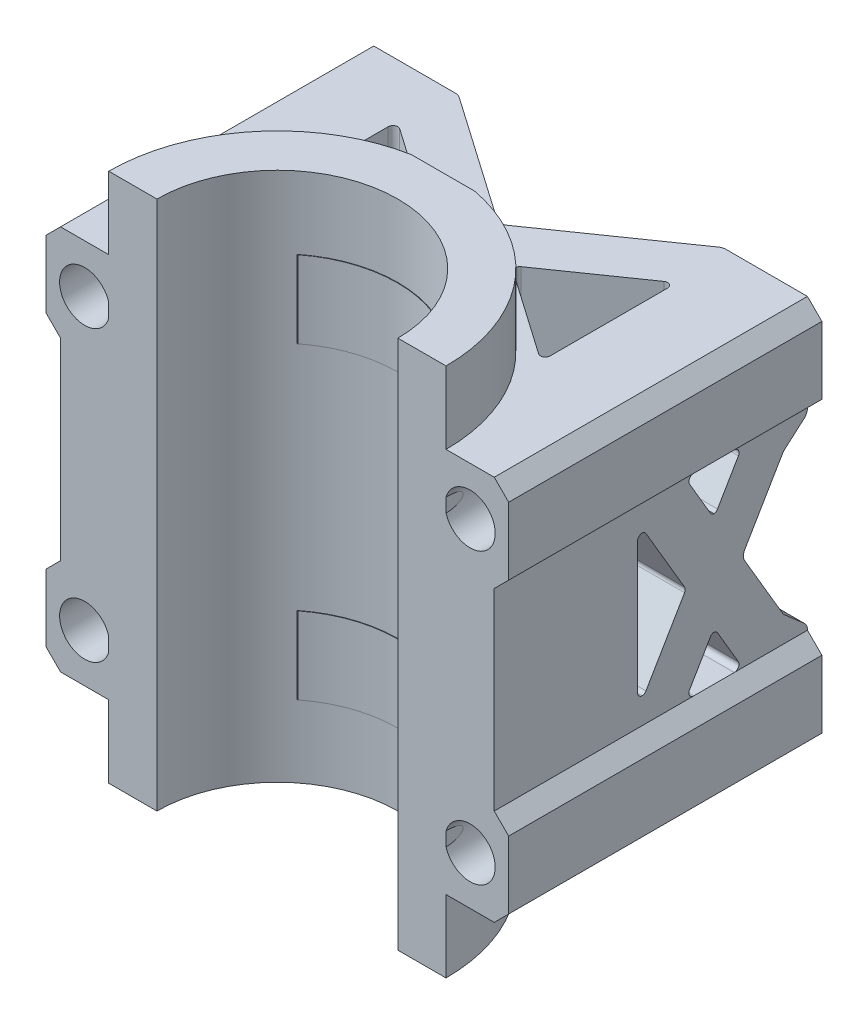
SolidWorks part; units mm, degrees
ref_plane "Front Plane" through (0, 0, 0) normal (0, 0, 1) x (1, 0, 0)
ref_plane "Top Plane" through (0, 0, 0) normal (0, 1, 0) x (1, 0, 0)
ref_plane "Right Plane" through (0, 0, 0) normal (1, 0, 0) x (0, 0, -1)
sketch "Sketch1" plane through (0, 0, 0) normal (0, 1, 0) x (1, 0, 0)
  line L0 (-12.5, 0) -> (-17.5, 0)
  line L1 (12.5, 0) -> (17.5, 0)
  line L2 (0, 0) -> (0, 12.5)
  line L4 (-0.3449, 17.192) -> (3.2687, 17.192)
  line L5 (3.2687, 17.192) -> (-3.2687, 17.192)
  arc A0 (12.5, 0) -> (-12.5, 0) centre (0, 0) ccw
  arc A1 (17.5, 0) -> (3.2687, 17.192) centre (0, 0) ccw
  arc A2 (-3.2687, 17.192) -> (-17.5, 0) centre (0, 0) ccw
  dimension "D1" = 25
  dimension "D2" = 35
extrude "Boss-Extrude1" add sketch "Sketch1" along normal blind 55 contours L5 A2 L0 A0 L1 A1 L4
sketch "Sketch4" plane through (0, 0, 0) normal (0, 0, 1) x (1, 0, 0)
  line L0 (0, -9.4556) -> (0, 9.4556) construction
  line L1 (-23.9986, 16.0014) -> (-22.5, 17.5)
  line L9 (-14.5, 27.5) -> (-19.9986, 27.5) construction
  line L24 (-23.9986, 8.9986) -> (-23.9986, 16.0014)
  line L27 (14.5, 7.5) -> (14.5, 12.5)
  line L41 (14.5, 37.5) -> (14.5, 42.5)
  line L46 (14.5, 12.5) -> (14.5, 17.5)
  line L47 (14.5, 12.5) -> (14.5, 7.5)
  line L48 (14.5, 7.5) -> (22.5, 7.5)
  line L49 (22.5, 7.5) -> (23.9986, 8.9986)
  line L50 (23.9986, 16.0014) -> (22.5, 17.5)
  line L51 (22.5, 17.5) -> (14.5, 17.5)
  line L52 (23.9986, 8.9986) -> (23.9986, 16.0014)
  line L53 (14.5, 37.5) -> (22.5, 37.5)
  line L54 (14.5, 42.5) -> (14.5, 37.5)
  line L55 (14.5, 42.5) -> (14.5, 47.5)
  line L56 (14.5, 47.5) -> (22.5, 47.5)
  line L57 (23.9986, 46.0014) -> (22.5, 47.5)
  line L58 (23.9986, 38.9986) -> (23.9986, 46.0014)
  line L59 (22.5, 37.5) -> (23.9986, 38.9986)
  line L60 (-22.5, 7.5) -> (-23.9986, 8.9986)
  line L61 (-14.5, 7.5) -> (-22.5, 7.5)
  line L62 (-14.5, 7.5) -> (-14.5, 12.5)
  line L63 (-14.5, 12.5) -> (-14.5, 17.5)
  line L64 (-22.5, 17.5) -> (-14.5, 17.5)
  line L65 (-22.5, 47.5) -> (-14.5, 47.5)
  line L66 (-23.9986, 46.0014) -> (-22.5, 47.5)
  line L67 (-23.9986, 38.9986) -> (-23.9986, 46.0014)
  line L68 (-22.5, 37.5) -> (-23.9986, 38.9986)
  line L69 (-14.5, 37.5) -> (-14.5, 42.5)
  line L70 (-14.5, 42.5) -> (-14.5, 47.5)
  line L71 (-14.5, 37.5) -> (-22.5, 37.5)
  circle A7 centre (19.9986, 12.5) radius 2.6
  circle A8 centre (19.9986, 42.5) radius 2.6
  circle A9 centre (-19.9986, 12.5) radius 2.6
  circle A10 centre (-19.9986, 42.5) radius 2.6
  dimension "D3" = 5.2
  dimension "D2" = 2
  dimension "D4" = 5.4986
  dimension "D10" = 2
  dimension "D9" = 2
extrude "Boss-Extrude2" add sketch "Sketch4" against normal blind 30
sketch "Sketch6" plane through (0, 37.5, 0) normal (0, -1, 0) x (1, 0, 0)
  line L1 (-22.5, 0) -> (-14.5, 0)
  line L2 (-22.5, 0) -> (-22.5, -30)
  line L3 (-22.5, -30) -> (-14.5, -30)
  line L4 (-14.5, 0) -> (-14.5, -30)
extrude "Boss-Extrude3" add sketch "Sketch6" along normal up to next
sketch "Sketch7" plane through (0, 37.5, 0) normal (0, -1, 0) x (1, 0, 0)
  line L1 (14.5, -30) -> (22.5, -30)
  line L2 (14.5, -30) -> (14.5, 0)
  line L3 (14.5, 0) -> (22.5, 0)
  line L4 (22.5, -30) -> (22.5, 0)
extrude "Boss-Extrude4" add sketch "Sketch7" along normal up to next
sketch "Sketch8" plane through (-14.5, 0, 0) normal (1, 0, 0) x (0, 0, -1)
  line L0 (9.798, 7.5) -> (9.798, 47.5) construction
  line L1 (30, 7.5) -> (9.798, 7.5)
  line L2 (30, 7.5) -> (30, 15.5)
  line L3 (30, 15.5) -> (9.798, 15.5)
  line L4 (9.798, 7.5) -> (9.798, 15.5)
  line L6 (30, 47.5) -> (9.798, 47.5)
  line L7 (30, 47.5) -> (30, 39.5)
  line L8 (30, 39.5) -> (9.798, 39.5)
  line L9 (9.798, 47.5) -> (9.798, 39.5)
  dimension "D1" = 8
  dimension "D2" = 8
extrude "Boss-Extrude5" add sketch "Sketch8" along normal up to next
sketch "Sketch9" plane through (0, 7.5, 0) normal (0, -1, 0) x (1, 0, 0)
  circle A0 centre (0, 0) radius 12.45
extrude "Cut-Extrude1" cut sketch "Sketch9" against normal blind 100
sketch "Sketch10" plane through (0, 39.5, 0) normal (0, -1, 0) x (1, 0, 0)
  line L0 (14.5, -9.798) -> (-14.5, -30) construction
  line L1 (-14.5, -9.798) -> (14.5, -30) construction
  line L2 (13.071, -7.7466) -> (-14.5, -26.9532)
  line L3 (14.5, -12.8448) -> (-10.1263, -30)
  line L4 (-14.5, -12.8448) -> (10.1263, -30)
  line L5 (-13.071, -7.7466) -> (14.5, -26.9532)
  line L6 (-10.4083, -30) -> (12.5196, -30)
  line L7 (14.5, -30) -> (-14.5, -30) construction
  line L8 (14.5, -27.9487) -> (14.5, -11.8493)
  line L9 (14.5, -9.798) -> (14.5, -30) construction
  line L10 (-14.5, -12.8448) -> (-14.5, -26.9532)
  line L12 (13.071, -7.7466) -> (-15.929, -27.9487) construction
  line L13 (15.929, -11.8493) -> (-13.071, -32.0513) construction
  line L14 (-15.929, -11.8493) -> (13.071, -32.0513) construction
  line L15 (-13.071, -7.7466) -> (15.929, -27.9487) construction
  line L16 (-14.5, -12.8448) -> (-14.5, -9.798)
  line L17 (-14.5, -26.9532) -> (-4.3737, -19.899)
  line L18 (-4.3737, -19.899) -> (-14.5, -12.8448)
  line L19 (-10.1263, -30) -> (10.1263, -30)
  line L20 (-10.1263, -30) -> (0, -22.9458)
  line L21 (0, -22.9458) -> (10.1263, -30)
  line L22 (14.5, -26.9532) -> (14.5, -12.8448)
  line L23 (14.5, -12.8448) -> (4.3737, -19.899)
  line L24 (4.3737, -19.899) -> (14.5, -26.9532)
  line M2 (14.5, -30) -> (14.5, -9.798)
  line M6 (-14.5, -9.798) -> (-14.5, -30)
  line M7 (-14.5, -30) -> (14.5, -30)
  dimension "D1" = 2.5
  dimension "D2" = 2.5
  dimension "D3" = 2.5
  dimension "D4" = 2.5
extrude "Cut-Extrude2" cut sketch "Sketch10" against normal mid plane 100 contours L3 L5 M2 | L4 L3 M7 | L4 L2 M6
sketch "Sketch11" plane through (-14.5, 0, 0) normal (1, 0, 0) x (0, 0, -1)
  line L0 (26.9532, 39.5) -> (29.4532, 39.5)
  line L1 (26.9532, 39.5) -> (30, 39.5) construction
  line L2 (26.9532, 15.5) -> (29.4532, 15.5)
  line L3 (30, 15.5) -> (26.9532, 15.5) construction
  line L4 (12.8448, 15.5) -> (10.3448, 15.5)
  line L5 (12.8448, 15.5) -> (9.798, 15.5) construction
  line L6 (12.8448, 39.5) -> (10.3448, 39.5)
  line L7 (9.798, 39.5) -> (12.8448, 39.5) construction
  line L8 (25.7775, 37.5) -> (14.0205, 17.5)
  line L9 (25.7775, 17.5) -> (14.0205, 37.5)
  line L10 (29.8219, 34.5136) -> (29.8219, 34.5136)
  line L11 (29.8219, 34.5136) -> (19.8204, 17.5)
  line L12 (15.7054, 10.5) -> (10.3448, 10.5)
  line L13 (29.8219, 20.4864) -> (29.8219, 20.4864)
  line L14 (29.8219, 20.4864) -> (19.8204, 37.5)
  line L15 (15.7054, 44.5) -> (10.3448, 44.5)
  line L17 (19.8204, 37.5) -> (22.7989, 32.4332)
  line L18 (22.7989, 32.4332) -> (25.7775, 37.5)
  line L19 (29.0236, 33.1557) -> (30, 34.8166)
  line L20 (29.0236, 21.8443) -> (29.8219, 20.4864)
  line L21 (29.0236, 21.8443) -> (30, 20.1848)
  line L22 (29.0236, 33.1557) -> (25.6989, 27.5)
  line L23 (25.6989, 27.5) -> (29.0236, 21.8443)
  line L24 (30, 34.8166) -> (30, 20.1848)
  line L25 (14.0205, 17.5) -> (14.0205, 37.5)
  line L26 (18.6447, 15.5) -> (12.8448, 15.5)
  line L27 (25.7775, 17.5) -> (22.7989, 22.5668)
  line L28 (22.7989, 22.5668) -> (19.8204, 17.5)
  line L30 (14.8757, 20.1848) -> (14.8757, 34.8166)
  line L31 (14.7882, 18.806) -> (14.8757, 20.1848)
  line L32 (14.0205, 17.5) -> (19.899, 27.5)
  line L33 (19.899, 27.5) -> (14.0205, 37.5)
  line L34 (14.0205, 37.5) -> (19.899, 27.5)
  line L35 (14.0205, 37.5) -> (19.899, 27.5)
  line L36 (26.9532, 15.5) -> (12.8448, 39.5) construction
  line L37 (30, 20.1848) -> (14.8757, 20.1848)
  line L38 (22.4028, 17.5) -> (25.7775, 17.5)
  line L39 (18.6447, 39.5) -> (15.7054, 44.5)
  line L40 (29.8219, 20.4864) -> (15.7054, 44.5) construction
  line L41 (26.9532, 39.5) -> (12.8448, 15.5) construction
  line L42 (30, 34.8166) -> (14.0205, 34.8166)
  line L43 (23.0244, 32.8166) -> (22.5735, 32.8166)
  line L44 (18.6447, 15.5) -> (15.7054, 10.5)
  line L45 (29.8219, 34.5136) -> (15.7054, 10.5) construction
  line L46 (22.4028, 17.5) -> (14.0205, 17.5)
  line L47 (30, 34.8166) -> (28.1141, 34.8166)
  line L48 (30, 34.8166) -> (30, 32.8166)
  line L49 (22.2819, 37.5) -> (25.7775, 37.5)
  line L50 (22.2819, 37.5) -> (14.0205, 37.5)
  line L54 (30, 20.1848) -> (27.9023, 20.1848)
  line L55 (30, 20.1848) -> (30, 22.1848)
  line L58 (23.0235, 22.1848) -> (22.5744, 22.1848)
  line M19 (30, 15.5) -> (30, 39.5)
  dimension "D1" = 2.5
  dimension "D2" = 2.5
  dimension "D3" = 2.5
  dimension "D4" = 5
  dimension "D5" = 5
extrude "Cut-Extrude15" cut sketch "Sketch11" against normal blind 10 contours L14 L21 L24 L19 L11 M19 | L43 L18 L42 L17 | L49 L50 L17 L42 L8 | L9 L42 L30 L37 L8 | L27 L58 L28 L37 | L46 L38 L9 L37 L28
mirror "Mirror1" about plane through (0, 0, 0) normal (1, 0, 0) of "Cut-Extrude15"
sketch "Sketch12" plane through (0, 0, -30) normal (0, 0, -1) x (-1, 0, 0)
  line L0 (10.1263, 15.5) -> (14.5, 15.5)
  line L1 (14.5, 15.5) -> (14.5, 20.1848)
  line L2 (14.5, 20.1848) -> (22.5, 20.1848)
  line L3 (22.5, 20.1848) -> (22.5, 17.5)
  line L4 (22.5, 17.5) -> (23.9986, 16.0014)
  line L5 (23.9986, 16.0014) -> (23.9986, 8.9986)
  line L6 (23.9986, 8.9986) -> (22.5, 7.5)
  line L7 (22.5, 7.5) -> (10.1263, 7.5)
  line L8 (10.1263, 7.5) -> (10.1263, 15.5)
  line L9 (-22.5, 17.5) -> (-22.5, 20.1848)
  line L10 (-22.5, 20.1848) -> (-14.5, 20.1848)
  line L11 (-14.5, 20.1848) -> (-14.5, 15.5)
  line L12 (-14.5, 15.5) -> (-10.1263, 15.5)
  line L13 (-10.1263, 15.5) -> (-10.1263, 7.5)
  line L14 (-10.1263, 7.5) -> (-22.5, 7.5)
  line L15 (-22.5, 7.5) -> (-23.9986, 8.9986)
  line L16 (-23.9986, 8.9986) -> (-23.9986, 16.0014)
  line L17 (-23.9986, 16.0014) -> (-22.5, 17.5)
  line L18 (-22.5, 37.5) -> (-23.9986, 38.9986)
  line L19 (-23.9986, 38.9986) -> (-23.9986, 46.0014)
  line L20 (-23.9986, 46.0014) -> (-22.5, 47.5)
  line L21 (-22.5, 47.5) -> (-10.1263, 47.5)
  line L22 (-10.1263, 47.5) -> (-10.1263, 39.5)
  line L23 (-10.1263, 39.5) -> (-14.5, 39.5)
  line L24 (-14.5, 39.5) -> (-14.5, 34.8166)
  line L25 (-14.5, 34.8166) -> (-22.5, 34.8166)
  line L26 (-22.5, 34.8166) -> (-22.5, 37.5)
  line L27 (10.1263, 47.5) -> (10.1263, 39.5)
  line L28 (10.1263, 39.5) -> (14.5, 39.5)
  line L29 (14.5, 39.5) -> (14.5, 34.8166)
  line L30 (14.5, 34.8166) -> (22.5, 34.8166)
  line L31 (22.5, 34.8166) -> (22.5, 37.5)
  line L32 (22.5, 37.5) -> (23.9986, 38.9986)
  line L33 (23.9986, 38.9986) -> (23.9986, 46.0014)
  line L34 (23.9986, 46.0014) -> (22.5, 47.5)
  line L35 (22.5, 47.5) -> (10.1263, 47.5)
extrude "Boss-Extrude6" add sketch "Sketch12" along normal blind 2.5
sketch "Sketch13" plane through (-22.5, 0, 0) normal (-1, 0, 0) x (0, 0, 1)
  line L0 (-32.5, 37.5) -> (-32.5, 37)
  line L1 (-32.5, 34.8166) -> (-32.5, 37.5) construction
  line L2 (-32.5, 37) -> (-30, 34.8166)
  line L6 (-32.5, 37) -> (-32.5, 34.8166)
  line L7 (-32.5, 34.8166) -> (-30, 34.8166)
  line L8 (-32.5, 17.5) -> (-32.5, 18)
  line L9 (-32.5, 17.5) -> (-32.5, 20.1848) construction
  line L10 (-32.5, 18) -> (-32.5, 20.1848)
  line L11 (-32.5, 20.1848) -> (-30, 20.1848)
  line L12 (-32.5, 18) -> (-30, 20.1848)
  line M18 (-32.5, 37.5) -> (-32.5, 34.8166)
  line M19 (-32.5, 34.8166) -> (-30, 34.8166)
  line M23 (-30, 20.1848) -> (-32.5, 20.1848)
  line M24 (-32.5, 20.1848) -> (-32.5, 17.5)
  dimension "D1" = 0.5
  dimension "D2" = 0.5
extrude "Cut-Extrude16" cut sketch "Sketch13" against normal through all contours L12 M24 M23 | L2 M18 M19
sketch "Sketch14" plane through (0, 47.5, 0) normal (0, 1, 0) x (1, 0, 0)
  line L0 (-10.1263, 30) -> (-13.7151, 32.5)
  line L1 (-22.5, 32.5) -> (-10.1263, 32.5) construction
  line L2 (-13.7151, 32.5) -> (-10.1263, 32.5)
  line L3 (-10.1263, 32.5) -> (-10.1263, 30)
  line L4 (10.1263, 30) -> (13.7151, 32.5)
  line L7 (10.1263, 32.5) -> (22.5, 32.5) construction
  line L8 (13.7151, 32.5) -> (10.1263, 32.5)
  line L9 (10.1263, 32.5) -> (10.1263, 30)
extrude "Cut-Extrude17" cut sketch "Sketch14" against normal through all
fillet "Fillet1" radius 1 16 edges at (0, 43.5, -22.9458) (0, 11.5, -22.9458) (-18.5, 27.5, -25.6989) (-18.5, 34.8166, -30) (-18.5, 20.1848, -30) (18.5, 27.5, -25.6989) (18.5, 20.1848, -30) (18.5, 34.8166, -30) (18.5, 18, -32.5) (-18.5, 18, -32.5) (18.5, 37, -32.5) (-18.5, 37, -32.5) (-13.7151, 11.5, -32.5) (-13.7151, 43.5, -32.5) (13.7151, 11.5, -32.5) (13.7151, 43.5, -32.5)
fillet "Fillet4" radius 0.5 54 edges at (-14.5, 43.5, -12.8448) (-14.5, 11.5, -12.8448) (-4.3737, 43.5, -19.899) (-4.3737, 11.5, -19.899) (-14.5, 43.5, -26.9532) (-14.5, 11.5, -26.9532) (4.3737, 43.5, -19.899) (4.3737, 11.5, -19.899) (14.5, 43.5, -12.8448) (14.5, 11.5, -12.8448) (14.5, 43.5, -26.9532) (14.5, 11.5, -26.9532) (-22.5, 22.1848, -22.7989) (-22.5, 32.8166, -22.7989) (-22.5, 34.8166, -15.2368) (-22.5, 20.1848, -15.2372) (-18.5, 34.8166, -15.5979) (-18.5, 27.5, -19.899) (-18.5, 20.1848, -15.5987) (-14.5, 20.1848, -15.2372) (-18.5, 20.1848, -14.8757) (-18.5, 34.8166, -14.8757) (-14.5, 34.8166, -15.2368) (-18.5, 32.8166, -23.0244) (-14.5, 32.8166, -22.7989) (-18.5, 32.8166, -22.5735) (-18.5, 37.5, -19.8204) (-18.5, 37.5, -25.7775) (-18.5, 22.1848, -23.0235) (-18.5, 17.5, -25.7775) (-18.5, 17.5, -19.8204) (-18.5, 22.1848, -22.5744) (-14.5, 22.1848, -22.7989) (22.5, 22.1848, -22.7989) (22.5, 32.8166, -22.7989) (22.5, 20.1848, -15.2372) (22.5, 34.8166, -15.2368) (18.5, 27.5, -19.899) (18.5, 34.8166, -15.5979) (14.5, 34.8166, -15.2368) (18.5, 34.8166, -14.8757) (18.5, 20.1848, -14.8757) (18.5, 20.1848, -15.5987) (14.5, 20.1848, -15.2372) (18.5, 32.8166, -22.5735) (18.5, 32.8166, -23.0244) (18.5, 37.5, -25.7775) (18.5, 37.5, -19.8204) (14.5, 32.8166, -22.7989) (18.5, 17.5, -25.7775) (18.5, 22.1848, -23.0235) (14.5, 22.1848, -22.7989) (18.5, 22.1848, -22.5744) (18.5, 17.5, -19.8204)
sketch "Sketch16" plane through (0, 0, -30) normal (0, 0, 1) x (1, 0, 0)
  circle A0 centre (-19.9986, 42.5) radius 2.6
  circle A1 centre (19.9986, 42.5) radius 2.6
  circle A2 centre (-19.9986, 12.5) radius 2.6
  circle A3 centre (19.9986, 12.5) radius 2.6
extrude "Cut-Extrude18" cut sketch "Sketch16" against normal through all
